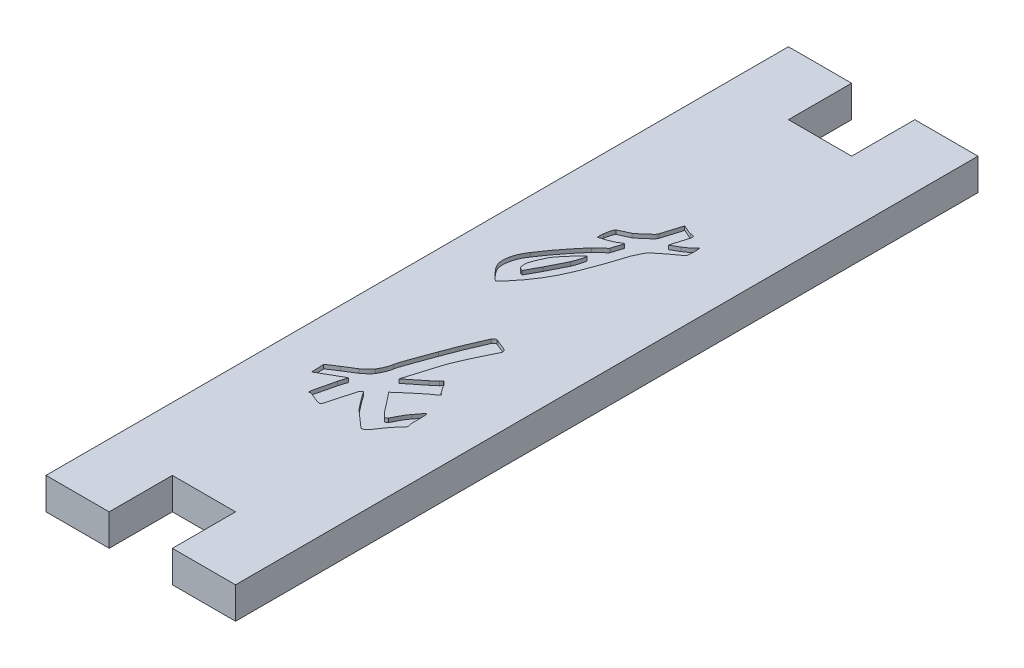
SolidWorks part; units mm, degrees
ref_plane "前基準面" through (0, 0, 0) normal (0, 0, 1) x (1, 0, 0)
ref_plane "上基準面" through (0, 0, 0) normal (0, 1, 0) x (1, 0, 0)
ref_plane "右基準面" through (0, 0, 0) normal (1, 0, 0) x (0, 0, -1)
sketch "草圖1" plane through (0, 0, 0) normal (0, 1, 0) x (1, 0, 0)
  line L0 (0, 39) -> (0, -39) construction
  line L1 (-12, 39) -> (12, 39)
  line L2 (-12, 39) -> (-12, -39)
  line L3 (-12, -39) -> (12, -39)
  line L4 (12, 39) -> (12, -39)
  line L5 (-12, 39) -> (12, -39) construction
  line L6 (-12, -39) -> (12, 39) construction
  line L7 (-4, 47) -> (-12, 47)
  line L8 (4, 39) -> (12, 39)
  line L9 (4, 39) -> (4, 47)
  line L10 (4, 47) -> (12, 47)
  line L11 (12, 39) -> (12, 47)
  line L12 (-12, 39) -> (-12, 47)
  line L13 (-4, 39) -> (-12, 39)
  line L14 (-4, 39) -> (-4, 47)
  line L15 (-12, 0) -> (12, 0) construction
  line L16 (4, -47) -> (12, -47)
  line L17 (12, -39) -> (12, -47)
  line L18 (4, -39) -> (12, -39)
  line L19 (4, -39) -> (4, -47)
  line L20 (-4, -39) -> (-4, -47)
  line L21 (-4, -39) -> (-12, -39)
  line L22 (-12, -39) -> (-12, -47)
  line L23 (-4, -47) -> (-12, -47)
  point P0 (0, 0)
  dimension "D1" = 78
  dimension "D2" = 24
  dimension "D3" = 8
  dimension "D4" = 8
  dimension "D5" = 4
extrude "填料-伸長1" add sketch "草圖1" along normal blind 4 contours L4 L1 L2 L3 | L23 L20 L3 L22 | L3 L19 L16 L17 | L1 L14 L7 L12 | L1 L11 L10 L9 region at (-8, 0, -43) region at (0, 0, 0) region at (-8, 0, 43) region at (8, 0, -43) region at (8, 0, 43)
sketch "草圖2" plane through (0, 4, 0) normal (0, 1, 0) x (1, 0, 0)
  line L0 (-12, 10) -> (12, 10) construction
  line L1 (-12, 47) -> (-12, -47) construction
  line L2 (12, 47) -> (12, -47) construction
  line L3 (-4, -39) -> (4, -39) construction
  dimension "D1" = 49
sketch "草圖3" plane through (0, 4, 0) normal (0, 1, 0) x (1, 0, 0)
  text T0 "j\r\nk" font "KINO 40" height 18
extrude "除料-伸長1" cut sketch "草圖3" against normal blind 0.5
